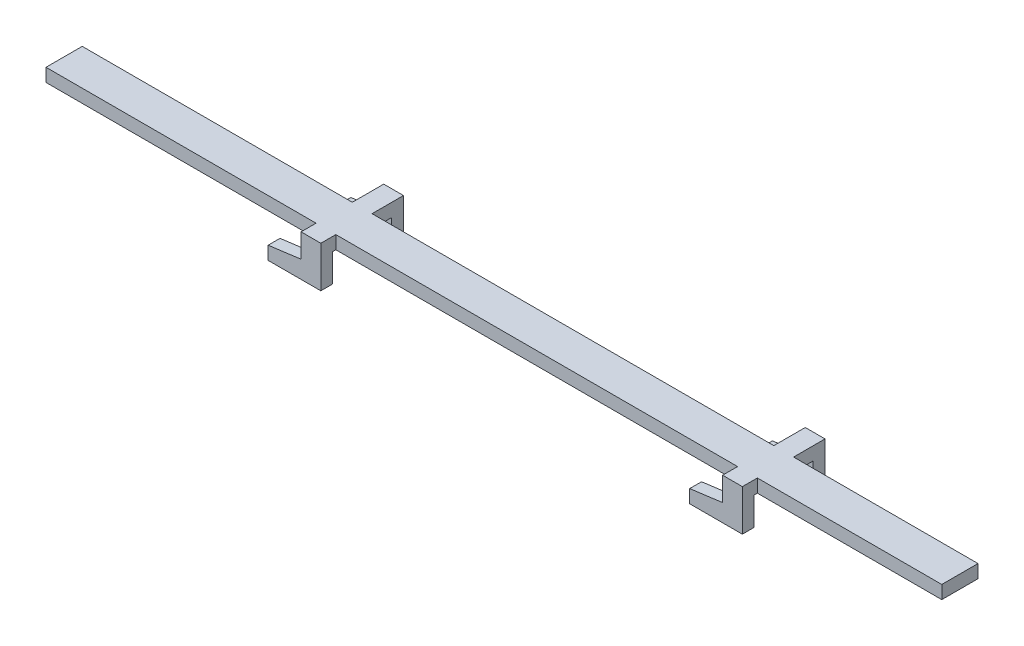
SolidWorks part; units mm, degrees
ref_plane "Top" through (0, 0, 0) normal (0, 0, 1) x (1, 0, 0)
ref_plane "Front" through (0, 0, 0) normal (0, 1, 0) x (1, 0, 0)
ref_plane "Right" through (0, 0, 0) normal (1, 0, 0) x (0, 0, -1)
sketch "Top Sketch" plane through (0, 0, 0) normal (0, 1, 0) x (1, 0, 0)
  line L0 (-28, -5.5) -> (-28, -6.875)
  line L1 (-136, 0) -> (-95, 0)
  line L2 (-136, 0) -> (-136, -5.5)
  line L3 (-136, -5.5) -> (-95, -5.5)
  line L4 (0, 0) -> (0, -5.5)
  line L5 (-28, -6.875) -> (-36, -6.875) construction
  line L6 (-36, -6.875) -> (-36, -5.5) construction
  line L7 (-92, -5.5) -> (-92, -6.875)
  line L8 (-92, -6.875) -> (-100, -6.875) construction
  line L9 (-100, -6.875) -> (-100, -5.5) construction
  line L10 (-28, 0) -> (-28, 3.875)
  line L11 (-28, 3.875) -> (-36, 3.875) construction
  line L12 (-36, 3.875) -> (-36, 0) construction
  line L13 (-92, 0) -> (-92, 3.875)
  line L14 (-92, 3.875) -> (-100, 3.875) construction
  line L15 (-100, 3.875) -> (-100, 0) construction
  line L16 (-28, 0) -> (0, 0)
  line L17 (-28, -5.5) -> (0, -5.5)
  line L18 (-92, 0) -> (-31, 0)
  line L19 (-92, -5.5) -> (-31, -5.5)
  line L20 (-31, 3.875) -> (-31, 0)
  line L21 (-31, 3.875) -> (-28, 3.875)
  line L22 (-31, -5.5) -> (-31, -6.875)
  line L23 (-31, -6.875) -> (-28, -6.875)
  line L24 (-95, 3.875) -> (-95, 0)
  line L25 (-95, 3.875) -> (-92, 3.875)
  line L26 (-95, -6.875) -> (-95, -5.5)
  line L27 (-95, -6.875) -> (-92, -6.875)
  line L28 (-136, -15.863) -> (0, -15.863) construction
  point P32 (-68, -15.863)
  dimension "D1" = 5.5
  dimension "Length" = 136
  dimension "D3" = 1.375
  dimension "D5" = 5
  dimension "D6" = 3.875
  dimension "D8" = 3
extrude "Thickness Extrude" add sketch "Top Sketch" along normal blind 2
sketch "Hook Sketch" plane through (0, 0, 6.875) normal (0, 0, 1) x (1, 0, 0)
  line L0 (-31, 2) -> (-28, 2)
  line L1 (-31, 0) -> (-28, 0) construction
  line L2 (-28, 2) -> (-28, -4.2583)
  line L3 (-28, -4.2583) -> (-36, -4.2583)
  line L4 (-36, -4.2583) -> (-36, -2.2583)
  line L5 (-36, -2.2583) -> (-31, -1.6)
  line L6 (-31, -1.6) -> (-31, 2)
  dimension "D1" = 7.5
  dimension "D2" = 5
  dimension "D3" = 1.6
  dimension "D4" = 2
extrude "Hook 1 Extrude" add sketch "Hook Sketch" against normal blind 0.9 and the other way blind 0.9 separate body
extrude "Hook 2 Extrude" add sketch "Hook Sketch<2>" along normal blind 0.9 and the other way blind 0.9 from surface separate body starting at face at (-29.5, 1, -3.875)
sketch "Hook Sketch<2>" plane through (0, 0, 6.875) normal (0, 0, 1) x (1, 0, 0) same geometry as "Hook Sketch"
pattern_linear "Hook Pattern" count 2 spacing 64 along (-1, 0, 0) of "Hook 1 Extrude", "Hook 2 Extrude"
combine bodies "Combine Bodies" operation type add bodies to combine 101 103 104 105 106
